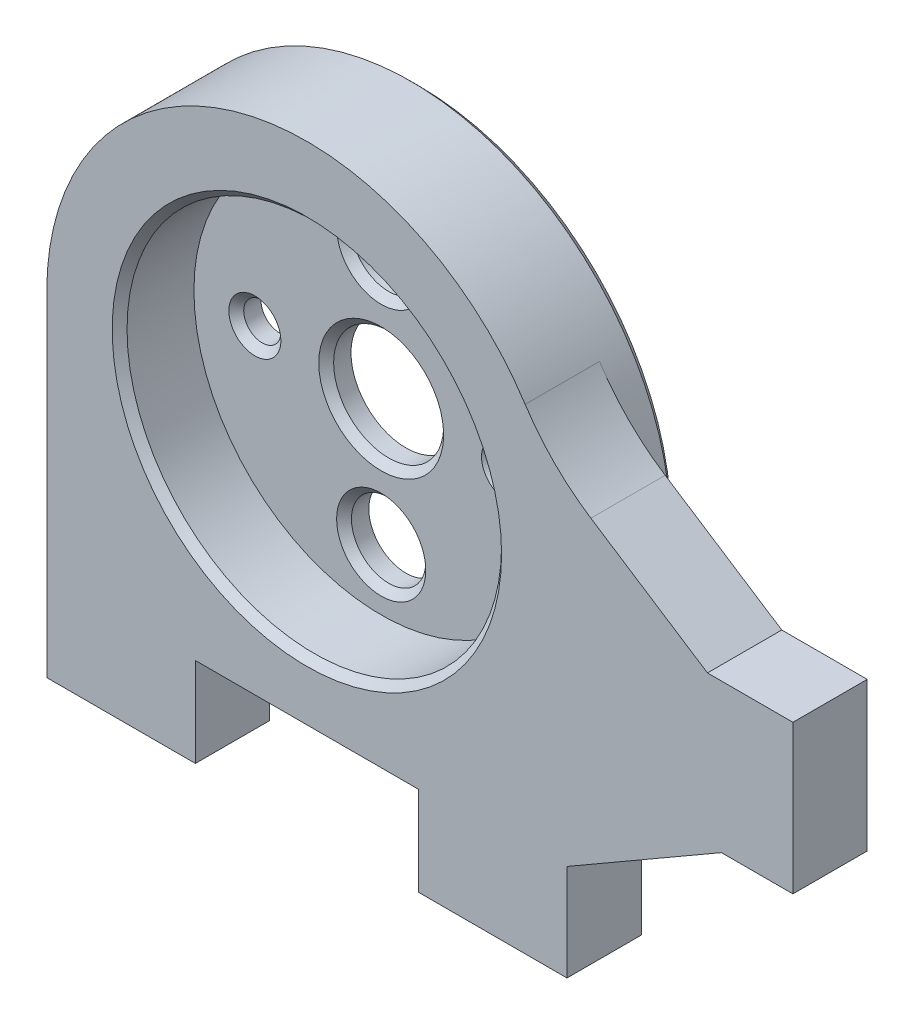
SolidWorks part; units mm, degrees
material "PBT General Purpose"
ref_plane "Front Plane" through (0, 0, 0) normal (0, 0, 1) x (1, 0, 0)
ref_plane "Top Plane" through (0, 0, 0) normal (0, 1, 0) x (1, 0, 0)
ref_plane "Right Plane" through (0, 0, 0) normal (1, 0, 0) x (0, 0, -1)
sketch "Sketch1" plane through (0, 0, 0) normal (0, 0, 1) x (1, 0, 0)
  line L0 (-17.5, -22.5) -> (-7.5, -22.5)
  line L4 (17.5, 0) -> (17.5, -22.5)
  line L10 (0, 17.5) -> (0, -22.5) construction
  line L11 (-17.5, 0) -> (-17.5, -22.5)
  line L12 (7.5, -22.5) -> (17.5, -22.5)
  line L14 (-7.5, -22.5) -> (-7.5, -16.5)
  line L15 (-7.5, -16.5) -> (7.5, -16.5)
  line L16 (7.5, -22.5) -> (7.5, -16.5)
  circle A0 centre (0, 0) radius 12.6
  arc A1 (17.5, 0) -> (-17.5, 0) centre (0, 0) ccw
  circle A2 centre (0, 0) radius 17.5 construction
  circle A3 centre (0, 0) radius 12.6 construction
  dimension "D1" = 25.2
  dimension "D3" = 22.5
  dimension "D4" = 6
  dimension "D5" = 10
  dimension "D2" = 4.9
extrude "Boss-Extrude1" add sketch "Sketch1" along normal mid plane 5
sketch "Sketch2" plane through (0, 0, 0) normal (0, 0, 1) x (1, 0, 0)
  line L0 (-17.5, 0) -> (-17.5, -22.5) construction
  line L1 (-17.5, -10) -> (-32.7, -10)
  line L2 (-17.5, -10) -> (-17.5, 0)
  line L3 (-17.5, 0) -> (-32.7, 0)
  line L4 (-32.7, -10) -> (-32.7, 0)
  dimension "D1" = 15.2
  dimension "D2" = 10
extrude "Boss-Extrude2" [suppressed] add sketch "Sketch2" along normal mid plane 5
sketch "Sketch3" plane through (0, 0, 0) normal (0, 0, 1) x (1, 0, 0)
  line L2 (17.5, -10) -> (17.5, 0)
  line L3 (17.5, 0) -> (32.7, 0)
  line L4 (32.7, -10) -> (32.7, 0)
  line L5 (17.5, -22.5) -> (17.5, 0) construction
  line L9 (32.7, -10) -> (17.5, -10)
  dimension "D1" = 15.2
  dimension "D2" = 10
extrude "Boss-Extrude3" add sketch "Sketch3" along normal mid plane 5
sketch "Sketch4" plane through (0, 0, -2.5) normal (0, 0, -1) x (-1, 0, 0)
  line L0 (7.5, -16.5) -> (-7.5, -16.5) construction
  line L1 (5.831, -16.5) -> (-5.831, -16.5)
  circle A0 centre (0, 0) radius 8.5 construction
  arc A1 (5.831, -16.5) -> (-5.831, -16.5) centre (0, 0) ccw
  circle A3 centre (0, 0) radius 12.6 construction
  circle A4 centre (0, 0) radius 3.5 construction
  circle A5 centre (-8.5, 0) radius 1.25
  circle A6 centre (8.5, 0) radius 1.25
  circle A7 centre (0, -8.5) radius 2.5
  circle A8 centre (0, 8.5) radius 2.5
  circle A9 centre (0, 0) radius 12.6 construction
  circle A10 centre (0, 0) radius 3.7
  arc A11 (17.5, 0) -> (-17.5, 0) centre (0, 0) ccw construction
  dimension "D2" = 17
  dimension "D3" = 2.5
  dimension "D4" = 5
  dimension "D5" = 0.2
  dimension "D6" = 7.4
extrude "Boss-Extrude4" add sketch "Sketch4" along normal blind 2.5
sketch "Sketch5" plane through (0, 0, -5) normal (0, 0, -1) x (-1, 0, 0)
  line L0 (-3.5, 8.5) -> (-4.7, 0)
  line L1 (-4.7, 0) -> (-3.5, -8.5)
  line L3 (4.7, 0) -> (3.5, -8.5)
  line L4 (3.5, 8.5) -> (4.7, 0)
  circle A0 centre (-8.5, 0) radius 2.25
  circle A1 centre (-8.5, 0) radius 1.25
  circle A2 centre (-8.5, 0) radius 1.25
  circle A3 centre (8.5, 0) radius 1.25
  circle A4 centre (8.5, 0) radius 1.25
  circle A5 centre (0, 0) radius 17.5 construction
  circle A11 centre (8.5, 0) radius 2.25
  arc A12 (-3.5, -8.5) -> (3.5, -8.5) centre (0, -8.5) ccw
  arc A13 (3.5, 8.5) -> (-3.5, 8.5) centre (0, 8.5) ccw
  arc A14 (-4.5163, 1.3011) -> (-4.5163, -1.3011) centre (0, 0) ccw
  arc A19 (4.5163, -1.3011) -> (4.5163, 1.3011) centre (0, 0) ccw
  circle M6 centre (0, 8.5) radius 2.5
  circle M7 centre (8.5, 0) radius 1.25
  circle M9 centre (-8.5, 0) radius 1.25
  circle M10 centre (0, -8.5) radius 2.5
  circle M11 centre (0, 0) radius 3.7
  dimension "D3" = 3.5
  dimension "D4" = 4.7
  dimension "D5" = 4.5163
  dimension "D1" = 0
  dimension "D2" = 0
  dimension "D6" = 1
extrude "Cut-Extrude1" cut sketch "Sketch5" against normal blind 0.8333 contours A0 M9 | L4 A13 L0 L1 A12 L3 M6 M10 M11 | A11 M7 region at (0, 11.7422, -5) region at (10.6864, 0, -5) region at (-6.3136, 0, -5)
chamfer "Chamfer1" distance 0.5 angle 45 10 edges at (4.1, 4.25, -5) (4.1, -4.25, -5) (0, -12, -5) (-4.1, -4.25, -5) (-4.1, 4.25, -5) (0, 12, -5) (-10.75, 0, -5) (0, 17.5, -5) (6.25, 0, -5) (0, -16.5, -5)
chamfer "Chamfer2" distance 0.5 angle 45 6 edges at (12.6, 0, 2.5) (-2.5, 8.5, -2.5) (-2.5, -8.5, -2.5) (-3.7, 0, -2.5) (7.25, 0, -2.5) (-9.75, 0, -2.5)
chamfer "Chamfer3" [suppressed] distance 12 angle 45
chamfer "Chamfer4" distance 12 angle 45 1 edges at (17.5, 0, 0)
fillet "Fillet2" radius 15 1 edges at (15.9867, 7.1186, 0)
fillet "Fillet3" [suppressed] radius 15
chamfer "Chamfer5" [suppressed] distance 6 angle 60
chamfer "Chamfer6" distance 6 angle 60 1 edges at (17.5, -10, 0) first distance on face at (17.5, -16.25, 0)
